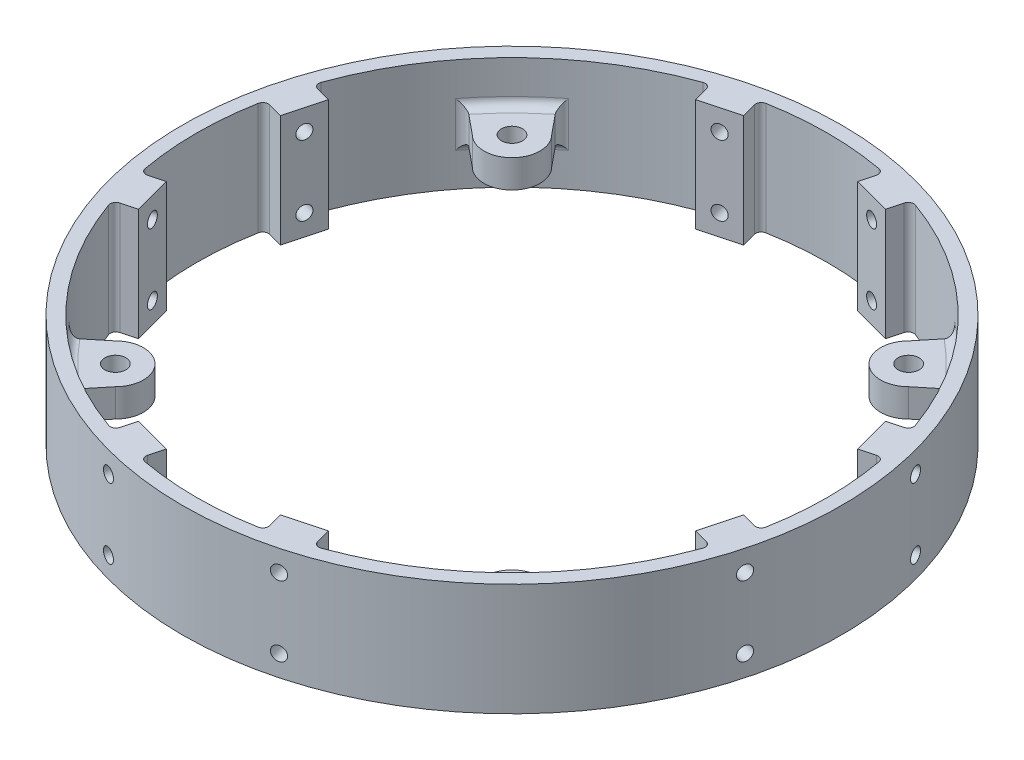
SolidWorks part; units mm, degrees
material "6061-T6 (SS)"
ref_plane "Front Plane" through (0, 0, 0) normal (0, 0, 1) x (1, 0, 0)
ref_plane "Top Plane" through (0, 0, 0) normal (0, 1, 0) x (1, 0, 0)
ref_plane "Right Plane" through (0, 0, 0) normal (1, 0, 0) x (0, 0, -1)
ref_axis "Axis of Revolution" through (0, -27.94, 0) along (0, 1, 0)
sketch "Sketch1" plane through (0, 0, 0) normal (0, 1, 0) x (1, 0, 0)
  line L0 (0, 149.225) -> (0, 0) construction
  line L1 (0, 0) -> (136.525, 0) construction
  line L2 (0, 0) -> (166.5143, 166.5143) construction
  line L3 (-617.3042, 796.9093) -> (89.8026, 89.8026) construction
  line L6 (0, 0) -> (51.1159, 190.7673) construction
  line L7 (0, 0) -> (78.0838, 135.2452) construction
  line L8 (101.0279, 101.0279) -> (93.1702, 93.1702)
  line L9 (86.435, 86.435) -> (80.8223, 80.8223)
  line L10 (80.8223, 98.7828) -> (62.9798, 109.0842) construction
  line L11 (80.8223, 98.7828) -> (90.4738, 110.5791)
  arc A10 (0, 149.225) -> (149.225, 0) centre (0, 0) cw construction
  arc A12 (93.1702, 93.1702) -> (86.435, 86.435) centre (89.8026, 89.8026) ccw
  arc A14 (0, 142.875) -> (142.875, 0) centre (0, 0) cw construction
  arc A15 (80.8223, 80.8223) -> (80.8223, 98.7828) centre (89.8026, 89.8026) cw
  arc A20 (71.4375, 123.7334) -> (101.0279, 101.0279) centre (0, 0) cw
  ellipse E0 centre (62.9798, 109.0842) end of major axis (80.8223, 98.7828) minor radius 16.9154 (71.4375, 123.7334) -> (80.8223, 98.7828) cw
  point P9 (74.6125, 129.2326)
  point P13 (71.4375, 123.7334)
  point P24 (80.8223, 80.8223)
  point P80 (0, 0)
  dimension "D8" = 9.525
  dimension "D1" = 149.225
  dimension "D3" = 127
  dimension "D4" = 45
  dimension "D5" = 12.7
  dimension "D2" = 30
  dimension "D6" = 15
  dimension "D7" = 6.35
extrude "Half of a Rod Holder (0.375\" Clearance)" add sketch "Sketch1" along normal blind 6.35 and the other way blind 6.35 contours L9 A12 region at (87.4048, 0, -96.8752)
mirror "Mirror Rod Holder" about plane through (0, -6.35, 0) normal (-0.7071, 0, -0.7071) of bodies 104
sketch "Sketch2" plane through (0, 0, 0) normal (0, 1, 0) x (1, 0, 0)
  line L2 (0, 0) -> (142.875, 0) construction
  line L3 (0, 0) -> (0, 142.875) construction
  line L4 (0, 142.875) -> (0, 149.225)
  line L5 (142.875, 0) -> (149.225, 0)
  arc A0 (149.225, 0) -> (0, 149.225) centre (0, 0) ccw
  arc A1 (142.875, 0) -> (0, 142.875) centre (0, 0) ccw
  dimension "D2" = 298.45
  dimension "D1" = 6.35
extrude "Quarter of Airframe Interface" add sketch "Sketch2" along normal blind 25.4 and the other way blind 25.4
fillet "Fillet for Rod Holder" radius 3.81 4 edges at (110.5791, 0, -90.4738) (101.0279, -6.35, -101.0279) (101.0279, 6.35, -101.0279) (90.4738, 0, -110.5791)
sketch "Sketch3" plane through (0, 0, 0) normal (0, 1, 0) x (1, 0, 0)
  line L0 (89.8026, 89.8026) -> (0, 0) construction
  line L2 (0, 0) -> (-146.317, -39.2055) construction
  line L4 (130.7238, 25.8237) -> (126.122, 42.9979)
  line L5 (126.122, 42.9979) -> (135.4383, 45.4942)
  line L6 (130.7238, 25.8237) -> (140.0401, 28.32)
  circle A9 centre (0, 0) radius 142.875 construction
  circle A10 centre (0, 0) radius 149.225 construction
  arc A11 (140.0401, 28.32) -> (135.4383, 45.4942) centre (0, 0) ccw
  circle A12 centre (89.8026, 89.8026) radius 4.7625 construction
  circle A16 centre (89.8026, 89.8026) radius 4.7625
  point P30 (128.4229, 34.4108)
  point P32 (144.1403, 38.6223)
  dimension "D3" = 17.78
  dimension "D4" = 16.2719
  dimension "D1" = 30
extrude "Radial Bolt Holder" add sketch "Sketch3" along normal up to surface (25.4 mm away) and the other way up to surface (25.4 mm away) contours L6 L5 | L4 L6 L5 region at (133.1705, 0, -35.6829) up to face at (88.149, 25.4, -88.149) other way up to face at (88.149, -25.4, -88.149)
sketch "Sketch4" plane through (128.4229, 0, -34.4108) normal (-0.9659, 0, 0.2588) x (0.2588, 0, 0.9659)
  line L0 (8.89, 25.4) -> (-8.89, 25.4) construction
  line L8 (-8.89, 6.35) -> (8.89, 6.35)
  line L9 (-8.89, 0) -> (8.89, 0) construction
  line L12 (-8.89, 25.4) -> (-8.89, -25.4) construction
  line L13 (-8.89, 25.4) -> (8.89, 6.35) construction
  line L14 (8.89, 25.4) -> (-8.89, 6.35) construction
  circle A0 centre (0, 15.875) radius 3.175
  circle A1 centre (0, -15.875) radius 3.175
  point P12 (-8.89, 0)
  dimension "D1" = 6.35
  dimension "D2" = 19.05
extrude "Radial Hole Cuts" cut sketch "Sketch4" against normal through all contours A1 | A0 region at (128.4229, -15.875, -34.4108)
ref_plane "Reflection Plane" through (0, 0, 0) normal (-0.7071, 0, -0.7071) x (-0.7071, 0, 0.7071)
mirror "Mirror Radial Bolt Holder" about plane through (0, 0, 0) normal (-0.7071, 0, -0.7071) of "Radial Hole Cuts", "Radial Bolt Holder"
fillet "Fillet for Radial Bolt Holders" radius 2.54 4 edges at (45.4942, 0, -135.4383) (28.32, 0, -140.0401) (135.4383, 0, -45.4942) (140.0401, 0, -28.32)
pattern_circular "CirPattern1" count 4 over 360 about axis through (0, -27.94, 0) along (0, 1, 0) of bodies 160
combine bodies "Combine1" bodies to combine 160 163 162 161
equation "\"Rocket Radius\"=6"
equation "\"Avionics Threaded Rod Diameter\"= 0.375in"
equation "\"D8@Sketch1\"=\"Avionics Threaded Rod Diameter\""
equation "\"Rocket Diameter\"= 12"
equation "\"D2@Sketch2\"=\"Rocket Diameter\"-(2*\"Airframe Thickness\")"
equation "\"Airframe Thickness\"= 0.125"
equation "\"D1@Sketch1\"=\"Rocket Radius\"-\"Airframe Thickness\""
equation "\"Bolt Flange Diameter\"= 19 / 32in"
equation "\"Bolt Height\"= 15 / 64in"
equation "\"D4@Sketch3\"=1-(\"Bolt Height\"+\"Airframe Thickness\")"
equation "\"Bolt Diameter\"=0.25"
equation "\"D1@Sketch4\"=\"Bolt Diameter\""
